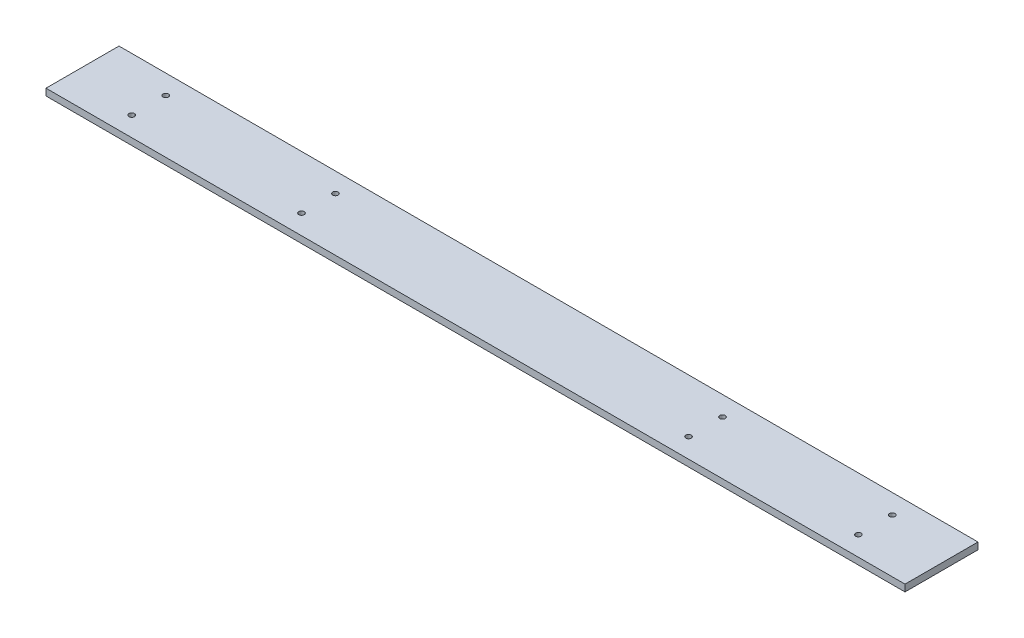
SolidWorks part; units mm, degrees
ref_plane "Front Plane" through (0, 0, 0) normal (0, 0, 1) x (1, 0, 0)
ref_plane "Top Plane" through (0, 0, 0) normal (0, 1, 0) x (1, 0, 0)
ref_plane "Right Plane" through (0, 0, 0) normal (1, 0, 0) x (0, 0, -1)
sketch "Sketch1" plane through (0, 0, 0) normal (0, 1, 0) x (1, 0, 0)
  line L1 (-253, -21.5) -> (253, -21.5)
  line L2 (-253, -21.5) -> (-253, 21.5)
  line L3 (-253, 21.5) -> (253, 21.5)
  line L4 (253, -21.5) -> (253, 21.5)
  line L5 (-253, -21.5) -> (253, 21.5) construction
  line L6 (-253, 21.5) -> (253, -21.5) construction
  point P0 (0, 0)
  dimension "D1" = 506
  dimension "D2" = 43
extrude "Boss-Extrude1" add sketch "Sketch1" along normal blind 4
sketch "expand_region" plane through (0, 4, 0) normal (0, 1, 0) x (1, 0, 0)
  line L0 (253, 21.5) -> (-253, 21.5) construction
  line L1 (-75, -21.5) -> (75, -21.5)
  line L2 (-75, -21.5) -> (-75, 21.5)
  line L3 (-75, 21.5) -> (75, 21.5)
  line L4 (75, -21.5) -> (75, 21.5)
  line L5 (-75, -21.5) -> (75, 21.5) construction
  line L6 (-75, 21.5) -> (75, -21.5) construction
  line L7 (0, 21.5) -> (0, -21.5)
  point P0 (0, 0)
  dimension "D1" = 150
sketch "Sketch3" plane through (0, 0, 0) normal (0, -1, 0) x (1, 0, 0)
  line L0 (75, 21.5) -> (75, -21.5) construction
  line L1 (75, 21.5) -> (75, -21.5) construction
  line L2 (75, 21.5) -> (253, -21.5) construction
  line L4 (114, -10) -> (214, -10) construction
  line L5 (114, -10) -> (114, 10) construction
  line L6 (114, 10) -> (214, 10) construction
  line L7 (214, -10) -> (214, 10) construction
  line L8 (114, -10) -> (214, 10) construction
  line L9 (114, 10) -> (214, -10) construction
  circle A0 centre (114, 10) radius 1.6
  circle A1 centre (214, 10) radius 1.6
  circle A2 centre (214, -10) radius 1.6
  circle A3 centre (114, -10) radius 1.6
  point P2 (164, 0)
  dimension "D1" = 3.2
  dimension "D2" = 100
  dimension "D3" = 20
extrude "Cut-Extrude1" cut sketch "Sketch3" against normal through all
mirror "Mirror1" about plane through (0, 0, 0) normal (1, 0, 0) of "Cut-Extrude1"
